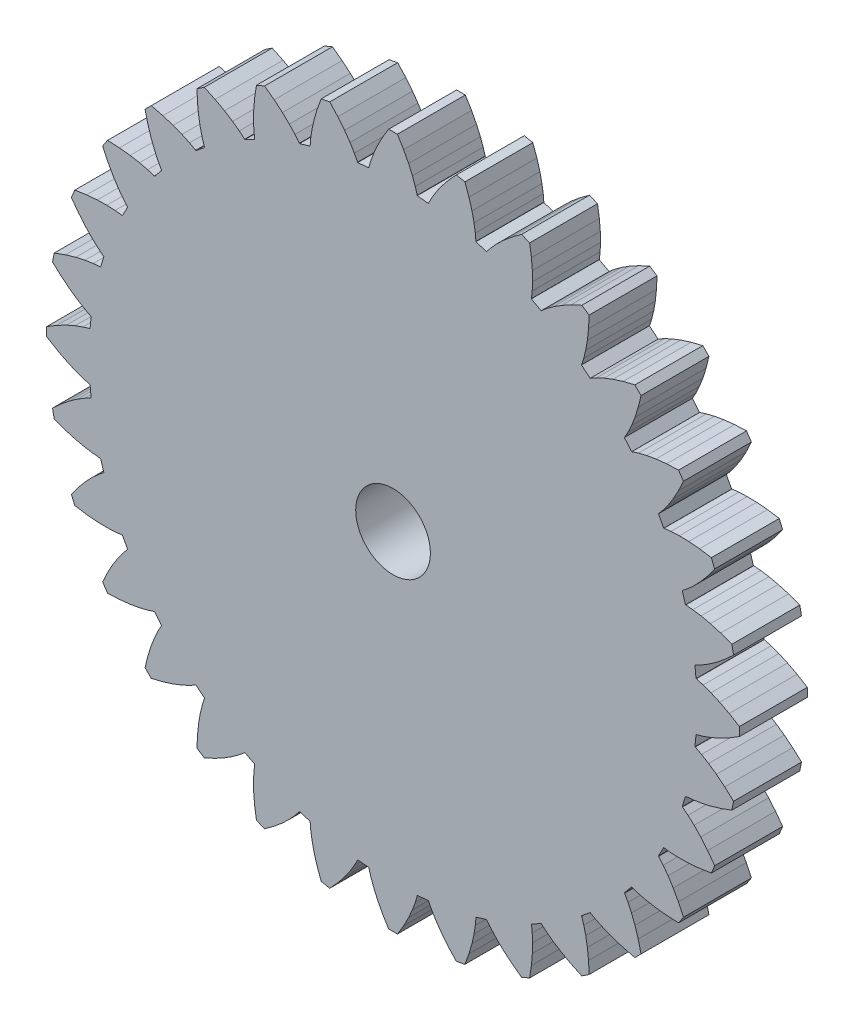
SolidWorks part; units mm, degrees
ref_plane "Front Plane" through (0, 0, 0) normal (0, 0, 1) x (1, 0, 0)
ref_plane "Top Plane" through (0, 0, 0) normal (0, 1, 0) x (1, 0, 0)
ref_plane "Right Plane" through (0, 0, 0) normal (1, 0, 0) x (0, 0, -1)
ref_plane "Plane1" through (0, 0, 5) normal (0, 0, 1) x (1, 0, 0)
sketch "Sketch1" plane through (0, 0, 5) normal (0, 0, 1) x (1, 0, 0)
  line L0 (1.7786, 22.3061) -> (1.7805, 22.3291)
  line L1 (1.7805, 22.3291) -> (1.6348, 22.8279)
  line L2 (1.6348, 22.8279) -> (1.426, 23.4012)
  line L3 (1.426, 23.4012) -> (1.1438, 24.0424)
  line L4 (1.1438, 24.0424) -> (0.7785, 24.7442)
  line L5 (0.7785, 24.7442) -> (0, 26.028)
  line L6 (0, 26.028) -> (-0.7785, 24.7442)
  line L7 (-0.7785, 24.7442) -> (-1.1437, 24.0424)
  line L8 (-1.1437, 24.0424) -> (-1.426, 23.4012)
  line L9 (-1.426, 23.4012) -> (-1.6348, 22.8279)
  line L10 (-1.6348, 22.8279) -> (-1.7805, 22.3291)
  line L11 (-1.7805, 22.3291) -> (-1.7786, 22.3061)
  line L12 (-1.7786, 22.3061) -> (-2.6072, 22.2245)
  line L13 (-2.6072, 22.2245) -> (-2.6099, 22.2474)
  line L14 (-2.6099, 22.2474) -> (-2.8501, 22.7082)
  line L15 (-2.8501, 22.7082) -> (-3.1668, 23.2297)
  line L16 (-3.1668, 23.2297) -> (-3.5687, 23.8036)
  line L17 (-3.5687, 23.8036) -> (-4.0638, 24.4206)
  line L18 (-4.0638, 24.4206) -> (-5.0778, 25.5278)
  line L19 (-5.0778, 25.5278) -> (-5.5909, 24.1168)
  line L20 (-5.5909, 24.1168) -> (-5.8122, 23.3573)
  line L21 (-5.8122, 23.3573) -> (-5.9639, 22.6733)
  line L22 (-5.9639, 22.6733) -> (-6.0569, 22.0703)
  line L23 (-6.0569, 22.0703) -> (-6.1025, 21.5527)
  line L24 (-6.1025, 21.5527) -> (-6.0962, 21.5305)
  line L25 (-6.0962, 21.5305) -> (-6.8929, 21.2888)
  line L26 (-6.8929, 21.2888) -> (-6.9, 21.3108)
  line L27 (-6.9, 21.3108) -> (-7.2255, 21.7159)
  line L28 (-7.2255, 21.7159) -> (-7.6378, 22.1656)
  line L29 (-7.6378, 22.1656) -> (-8.1439, 22.65)
  line L30 (-8.1439, 22.65) -> (-8.7499, 23.1586)
  line L31 (-8.7499, 23.1586) -> (-9.9605, 24.0466)
  line L32 (-9.9605, 24.0466) -> (-10.1884, 22.5627)
  line L33 (-10.1884, 22.5627) -> (-10.2573, 21.7746)
  line L34 (-10.2573, 21.7746) -> (-10.2727, 21.0742)
  line L35 (-10.2727, 21.0742) -> (-10.2462, 20.4646)
  line L36 (-10.2462, 20.4646) -> (-10.1899, 19.948)
  line L37 (-10.1899, 19.948) -> (-10.1794, 19.9275)
  line L38 (-10.1794, 19.9275) -> (-10.9137, 19.535)
  line L39 (-10.9137, 19.535) -> (-10.925, 19.5551)
  line L40 (-10.925, 19.5551) -> (-11.3232, 19.889)
  line L41 (-11.3232, 19.889) -> (-11.8153, 20.2496)
  line L42 (-11.8153, 20.2496) -> (-12.4062, 20.626)
  line L43 (-12.4062, 20.626) -> (-13.0998, 21.0065)
  line L44 (-13.0998, 21.0065) -> (-14.4603, 21.6414)
  line L45 (-14.4603, 21.6414) -> (-14.3944, 20.1415)
  line L46 (-14.3944, 20.1415) -> (-14.3082, 19.3551)
  line L47 (-14.3082, 19.3551) -> (-14.1866, 18.6651)
  line L48 (-14.1866, 18.6651) -> (-14.0418, 18.0724)
  line L49 (-14.0418, 18.0724) -> (-13.8858, 17.5768)
  line L50 (-13.8858, 17.5768) -> (-13.8715, 17.5587)
  line L51 (-13.8715, 17.5587) -> (-14.5151, 17.0305)
  line L52 (-14.5151, 17.0305) -> (-14.5301, 17.048)
  line L53 (-14.5301, 17.048) -> (-14.9858, 17.2977)
  line L54 (-14.9858, 17.2977) -> (-15.5388, 17.5555)
  line L55 (-15.5388, 17.5555) -> (-16.1918, 17.8093)
  line L56 (-16.1918, 17.8093) -> (-16.9463, 18.0473)
  line L57 (-16.9463, 18.0473) -> (-18.4044, 18.4044)
  line L58 (-18.4044, 18.4044) -> (-18.0473, 16.9463)
  line L59 (-18.0473, 16.9463) -> (-17.8093, 16.1918)
  line L60 (-17.8093, 16.1918) -> (-17.5555, 15.5388)
  line L61 (-17.5555, 15.5388) -> (-17.2977, 14.9858)
  line L62 (-17.2977, 14.9858) -> (-17.048, 14.5301)
  line L63 (-17.048, 14.5301) -> (-17.0305, 14.5151)
  line L64 (-17.0305, 14.5151) -> (-17.5587, 13.8715)
  line L65 (-17.5587, 13.8715) -> (-17.5768, 13.8858)
  line L66 (-17.5768, 13.8858) -> (-18.0724, 14.0418)
  line L67 (-18.0724, 14.0418) -> (-18.6651, 14.1866)
  line L68 (-18.6651, 14.1866) -> (-19.3551, 14.3082)
  line L69 (-19.3551, 14.3082) -> (-20.1415, 14.3944)
  line L70 (-20.1415, 14.3944) -> (-21.6414, 14.4603)
  line L71 (-21.6414, 14.4603) -> (-21.0065, 13.0998)
  line L72 (-21.0065, 13.0998) -> (-20.626, 12.4062)
  line L73 (-20.626, 12.4062) -> (-20.2496, 11.8153)
  line L74 (-20.2496, 11.8153) -> (-19.889, 11.3232)
  line L75 (-19.889, 11.3232) -> (-19.5551, 10.925)
  line L76 (-19.5551, 10.925) -> (-19.535, 10.9137)
  line L77 (-19.535, 10.9137) -> (-19.9275, 10.1794)
  line L78 (-19.9275, 10.1794) -> (-19.948, 10.1899)
  line L79 (-19.948, 10.1899) -> (-20.4646, 10.2462)
  line L80 (-20.4646, 10.2462) -> (-21.0742, 10.2727)
  line L81 (-21.0742, 10.2727) -> (-21.7746, 10.2573)
  line L82 (-21.7746, 10.2573) -> (-22.5627, 10.1884)
  line L83 (-22.5627, 10.1884) -> (-24.0466, 9.9605)
  line L84 (-24.0466, 9.9605) -> (-23.1586, 8.7499)
  line L85 (-23.1586, 8.7499) -> (-22.65, 8.1439)
  line L86 (-22.65, 8.1439) -> (-22.1656, 7.6378)
  line L87 (-22.1656, 7.6378) -> (-21.7159, 7.2255)
  line L88 (-21.7159, 7.2255) -> (-21.3108, 6.9)
  line L89 (-21.3108, 6.9) -> (-21.2888, 6.8929)
  line L90 (-21.2888, 6.8929) -> (-21.5305, 6.0962)
  line L91 (-21.5305, 6.0962) -> (-21.5527, 6.1025)
  line L92 (-21.5527, 6.1025) -> (-22.0703, 6.0569)
  line L93 (-22.0703, 6.0569) -> (-22.6733, 5.9639)
  line L94 (-22.6733, 5.9639) -> (-23.3573, 5.8122)
  line L95 (-23.3573, 5.8122) -> (-24.1168, 5.5909)
  line L96 (-24.1168, 5.5909) -> (-25.5278, 5.0778)
  line L97 (-25.5278, 5.0778) -> (-24.4206, 4.0638)
  line L98 (-24.4206, 4.0638) -> (-23.8036, 3.5687)
  line L99 (-23.8036, 3.5687) -> (-23.2297, 3.1668)
  line L100 (-23.2297, 3.1668) -> (-22.7082, 2.8501)
  line L101 (-22.7082, 2.8501) -> (-22.2474, 2.6099)
  line L102 (-22.2474, 2.6099) -> (-22.2245, 2.6072)
  line L103 (-22.2245, 2.6072) -> (-22.3061, 1.7786)
  line L104 (-22.3061, 1.7786) -> (-22.3291, 1.7805)
  line L105 (-22.3291, 1.7805) -> (-22.8279, 1.6348)
  line L106 (-22.8279, 1.6348) -> (-23.4012, 1.426)
  line L107 (-23.4012, 1.426) -> (-24.0424, 1.1438)
  line L108 (-24.0424, 1.1438) -> (-24.7442, 0.7785)
  line L109 (-24.7442, 0.7785) -> (-26.028, 0)
  line L110 (-26.028, 0) -> (-24.7442, -0.7785)
  line L111 (-24.7442, -0.7785) -> (-24.0424, -1.1437)
  line L112 (-24.0424, -1.1437) -> (-23.4012, -1.426)
  line L113 (-23.4012, -1.426) -> (-22.8279, -1.6348)
  line L114 (-22.8279, -1.6348) -> (-22.3291, -1.7805)
  line L115 (-22.3291, -1.7805) -> (-22.3061, -1.7786)
  line L116 (-22.3061, -1.7786) -> (-22.2245, -2.6072)
  line L117 (-22.2245, -2.6072) -> (-22.2474, -2.6099)
  line L118 (-22.2474, -2.6099) -> (-22.7082, -2.8501)
  line L119 (-22.7082, -2.8501) -> (-23.2297, -3.1668)
  line L120 (-23.2297, -3.1668) -> (-23.8036, -3.5687)
  line L121 (-23.8036, -3.5687) -> (-24.4206, -4.0638)
  line L122 (-24.4206, -4.0638) -> (-25.5278, -5.0778)
  line L123 (-25.5278, -5.0778) -> (-24.1168, -5.5909)
  line L124 (-24.1168, -5.5909) -> (-23.3573, -5.8122)
  line L125 (-23.3573, -5.8122) -> (-22.6733, -5.9639)
  line L126 (-22.6733, -5.9639) -> (-22.0703, -6.0569)
  line L127 (-22.0703, -6.0569) -> (-21.5527, -6.1025)
  line L128 (-21.5527, -6.1025) -> (-21.5305, -6.0962)
  line L129 (-21.5305, -6.0962) -> (-21.2888, -6.8929)
  line L130 (-21.2888, -6.8929) -> (-21.3108, -6.9)
  line L131 (-21.3108, -6.9) -> (-21.7159, -7.2255)
  line L132 (-21.7159, -7.2255) -> (-22.1656, -7.6378)
  line L133 (-22.1656, -7.6378) -> (-22.65, -8.1439)
  line L134 (-22.65, -8.1439) -> (-23.1586, -8.7499)
  line L135 (-23.1586, -8.7499) -> (-24.0466, -9.9605)
  line L136 (-24.0466, -9.9605) -> (-22.5627, -10.1884)
  line L137 (-22.5627, -10.1884) -> (-21.7746, -10.2573)
  line L138 (-21.7746, -10.2573) -> (-21.0742, -10.2727)
  line L139 (-21.0742, -10.2727) -> (-20.4646, -10.2462)
  line L140 (-20.4646, -10.2462) -> (-19.948, -10.1899)
  line L141 (-19.948, -10.1899) -> (-19.9275, -10.1794)
  line L142 (-19.9275, -10.1794) -> (-19.535, -10.9137)
  line L143 (-19.535, -10.9137) -> (-19.5551, -10.925)
  line L144 (-19.5551, -10.925) -> (-19.889, -11.3232)
  line L145 (-19.889, -11.3232) -> (-20.2496, -11.8153)
  line L146 (-20.2496, -11.8153) -> (-20.626, -12.4062)
  line L147 (-20.626, -12.4062) -> (-21.0065, -13.0998)
  line L148 (-21.0065, -13.0998) -> (-21.6414, -14.4603)
  line L149 (-21.6414, -14.4603) -> (-20.1415, -14.3944)
  line L150 (-20.1415, -14.3944) -> (-19.3551, -14.3082)
  line L151 (-19.3551, -14.3082) -> (-18.6651, -14.1866)
  line L152 (-18.6651, -14.1866) -> (-18.0724, -14.0418)
  line L153 (-18.0724, -14.0418) -> (-17.5768, -13.8858)
  line L154 (-17.5768, -13.8858) -> (-17.5587, -13.8715)
  line L155 (-17.5587, -13.8715) -> (-17.0305, -14.5151)
  line L156 (-17.0305, -14.5151) -> (-17.048, -14.5301)
  line L157 (-17.048, -14.5301) -> (-17.2977, -14.9858)
  line L158 (-17.2977, -14.9858) -> (-17.5555, -15.5388)
  line L159 (-17.5555, -15.5388) -> (-17.8093, -16.1918)
  line L160 (-17.8093, -16.1918) -> (-18.0473, -16.9463)
  line L161 (-18.0473, -16.9463) -> (-18.4044, -18.4044)
  line L162 (-18.4044, -18.4044) -> (-16.9463, -18.0473)
  line L163 (-16.9463, -18.0473) -> (-16.1918, -17.8093)
  line L164 (-16.1918, -17.8093) -> (-15.5388, -17.5555)
  line L165 (-15.5388, -17.5555) -> (-14.9858, -17.2977)
  line L166 (-14.9858, -17.2977) -> (-14.5301, -17.048)
  line L167 (-14.5301, -17.048) -> (-14.5151, -17.0305)
  line L168 (-14.5151, -17.0305) -> (-13.8715, -17.5587)
  line L169 (-13.8715, -17.5587) -> (-13.8858, -17.5768)
  line L170 (-13.8858, -17.5768) -> (-14.0418, -18.0724)
  line L171 (-14.0418, -18.0724) -> (-14.1866, -18.6651)
  line L172 (-14.1866, -18.6651) -> (-14.3082, -19.3551)
  line L173 (-14.3082, -19.3551) -> (-14.3944, -20.1415)
  line L174 (-14.3944, -20.1415) -> (-14.4603, -21.6414)
  line L175 (-14.4603, -21.6414) -> (-13.0998, -21.0065)
  line L176 (-13.0998, -21.0065) -> (-12.4062, -20.626)
  line L177 (-12.4062, -20.626) -> (-11.8153, -20.2496)
  line L178 (-11.8153, -20.2496) -> (-11.3232, -19.889)
  line L179 (-11.3232, -19.889) -> (-10.925, -19.5551)
  line L180 (-10.925, -19.5551) -> (-10.9137, -19.535)
  line L181 (-10.9137, -19.535) -> (-10.1794, -19.9275)
  line L182 (-10.1794, -19.9275) -> (-10.1899, -19.948)
  line L183 (-10.1899, -19.948) -> (-10.2462, -20.4646)
  line L184 (-10.2462, -20.4646) -> (-10.2727, -21.0742)
  line L185 (-10.2727, -21.0742) -> (-10.2573, -21.7746)
  line L186 (-10.2573, -21.7746) -> (-10.1884, -22.5627)
  line L187 (-10.1884, -22.5627) -> (-9.9605, -24.0466)
  line L188 (-9.9605, -24.0466) -> (-8.7499, -23.1586)
  line L189 (-8.7499, -23.1586) -> (-8.1439, -22.65)
  line L190 (-8.1439, -22.65) -> (-7.6378, -22.1656)
  line L191 (-7.6378, -22.1656) -> (-7.2255, -21.7159)
  line L192 (-7.2255, -21.7159) -> (-6.9, -21.3108)
  line L193 (-6.9, -21.3108) -> (-6.8929, -21.2888)
  line L194 (-6.8929, -21.2888) -> (-6.0962, -21.5305)
  line L195 (-6.0962, -21.5305) -> (-6.1025, -21.5527)
  line L196 (-6.1025, -21.5527) -> (-6.0569, -22.0703)
  line L197 (-6.0569, -22.0703) -> (-5.9639, -22.6733)
  line L198 (-5.9639, -22.6733) -> (-5.8122, -23.3573)
  line L199 (-5.8122, -23.3573) -> (-5.5909, -24.1168)
  line L200 (-5.5909, -24.1168) -> (-5.0778, -25.5278)
  line L201 (-5.0778, -25.5278) -> (-4.0638, -24.4206)
  line L202 (-4.0638, -24.4206) -> (-3.5687, -23.8036)
  line L203 (-3.5687, -23.8036) -> (-3.1668, -23.2297)
  line L204 (-3.1668, -23.2297) -> (-2.8501, -22.7082)
  line L205 (-2.8501, -22.7082) -> (-2.6099, -22.2474)
  line L206 (-2.6099, -22.2474) -> (-2.6072, -22.2245)
  line L207 (-2.6072, -22.2245) -> (-1.7786, -22.3061)
  line L208 (-1.7786, -22.3061) -> (-1.7805, -22.3291)
  line L209 (-1.7805, -22.3291) -> (-1.6348, -22.8279)
  line L210 (-1.6348, -22.8279) -> (-1.426, -23.4012)
  line L211 (-1.426, -23.4012) -> (-1.1438, -24.0424)
  line L212 (-1.1438, -24.0424) -> (-0.7785, -24.7442)
  line L213 (-0.7785, -24.7442) -> (0, -26.028)
  line L214 (0, -26.028) -> (0.7785, -24.7442)
  line L215 (0.7785, -24.7442) -> (1.1437, -24.0424)
  line L216 (1.1437, -24.0424) -> (1.426, -23.4012)
  line L217 (1.426, -23.4012) -> (1.6348, -22.8279)
  line L218 (1.6348, -22.8279) -> (1.7805, -22.3291)
  line L219 (1.7805, -22.3291) -> (1.7786, -22.3061)
  line L220 (1.7786, -22.3061) -> (2.6072, -22.2245)
  line L221 (2.6072, -22.2245) -> (2.6099, -22.2474)
  line L222 (2.6099, -22.2474) -> (2.8501, -22.7082)
  line L223 (2.8501, -22.7082) -> (3.1668, -23.2297)
  line L224 (3.1668, -23.2297) -> (3.5687, -23.8036)
  line L225 (3.5687, -23.8036) -> (4.0638, -24.4206)
  line L226 (4.0638, -24.4206) -> (5.0778, -25.5278)
  line L227 (5.0778, -25.5278) -> (5.5909, -24.1168)
  line L228 (5.5909, -24.1168) -> (5.8122, -23.3573)
  line L229 (5.8122, -23.3573) -> (5.9639, -22.6733)
  line L230 (5.9639, -22.6733) -> (6.0569, -22.0703)
  line L231 (6.0569, -22.0703) -> (6.1025, -21.5527)
  line L232 (6.1025, -21.5527) -> (6.0962, -21.5305)
  line L233 (6.0962, -21.5305) -> (6.8929, -21.2888)
  line L234 (6.8929, -21.2888) -> (6.9, -21.3108)
  line L235 (6.9, -21.3108) -> (7.2255, -21.7159)
  line L236 (7.2255, -21.7159) -> (7.6378, -22.1656)
  line L237 (7.6378, -22.1656) -> (8.1439, -22.65)
  line L238 (8.1439, -22.65) -> (8.7499, -23.1586)
  line L239 (8.7499, -23.1586) -> (9.9605, -24.0466)
  line L240 (9.9605, -24.0466) -> (10.1884, -22.5627)
  line L241 (10.1884, -22.5627) -> (10.2573, -21.7746)
  line L242 (10.2573, -21.7746) -> (10.2727, -21.0742)
  line L243 (10.2727, -21.0742) -> (10.2462, -20.4646)
  line L244 (10.2462, -20.4646) -> (10.1899, -19.948)
  line L245 (10.1899, -19.948) -> (10.1794, -19.9275)
  line L246 (10.1794, -19.9275) -> (10.9137, -19.535)
  line L247 (10.9137, -19.535) -> (10.925, -19.5551)
  line L248 (10.925, -19.5551) -> (11.3232, -19.889)
  line L249 (11.3232, -19.889) -> (11.8153, -20.2496)
  line L250 (11.8153, -20.2496) -> (12.4062, -20.626)
  line L251 (12.4062, -20.626) -> (13.0998, -21.0065)
  line L252 (13.0998, -21.0065) -> (14.4603, -21.6414)
  line L253 (14.4603, -21.6414) -> (14.3944, -20.1415)
  line L254 (14.3944, -20.1415) -> (14.3082, -19.3551)
  line L255 (14.3082, -19.3551) -> (14.1866, -18.6651)
  line L256 (14.1866, -18.6651) -> (14.0418, -18.0724)
  line L257 (14.0418, -18.0724) -> (13.8858, -17.5768)
  line L258 (13.8858, -17.5768) -> (13.8715, -17.5587)
  line L259 (13.8715, -17.5587) -> (14.5151, -17.0305)
  line L260 (14.5151, -17.0305) -> (14.5301, -17.048)
  line L261 (14.5301, -17.048) -> (14.9858, -17.2977)
  line L262 (14.9858, -17.2977) -> (15.5388, -17.5555)
  line L263 (15.5388, -17.5555) -> (16.1918, -17.8093)
  line L264 (16.1918, -17.8093) -> (16.9463, -18.0473)
  line L265 (16.9463, -18.0473) -> (18.4044, -18.4044)
  line L266 (18.4044, -18.4044) -> (18.0473, -16.9463)
  line L267 (18.0473, -16.9463) -> (17.8093, -16.1918)
  line L268 (17.8093, -16.1918) -> (17.5555, -15.5388)
  line L269 (17.5555, -15.5388) -> (17.2977, -14.9858)
  line L270 (17.2977, -14.9858) -> (17.048, -14.5301)
  line L271 (17.048, -14.5301) -> (17.0305, -14.5151)
  line L272 (17.0305, -14.5151) -> (17.5587, -13.8715)
  line L273 (17.5587, -13.8715) -> (17.5768, -13.8858)
  line L274 (17.5768, -13.8858) -> (18.0724, -14.0418)
  line L275 (18.0724, -14.0418) -> (18.6651, -14.1866)
  line L276 (18.6651, -14.1866) -> (19.3551, -14.3082)
  line L277 (19.3551, -14.3082) -> (20.1415, -14.3944)
  line L278 (20.1415, -14.3944) -> (21.6414, -14.4603)
  line L279 (21.6414, -14.4603) -> (21.0065, -13.0998)
  line L280 (21.0065, -13.0998) -> (20.626, -12.4062)
  line L281 (20.626, -12.4062) -> (20.2496, -11.8153)
  line L282 (20.2496, -11.8153) -> (19.889, -11.3232)
  line L283 (19.889, -11.3232) -> (19.5551, -10.925)
  line L284 (19.5551, -10.925) -> (19.535, -10.9137)
  line L285 (19.535, -10.9137) -> (19.9275, -10.1794)
  line L286 (19.9275, -10.1794) -> (19.948, -10.1899)
  line L287 (19.948, -10.1899) -> (20.4646, -10.2462)
  line L288 (20.4646, -10.2462) -> (21.0742, -10.2727)
  line L289 (21.0742, -10.2727) -> (21.7746, -10.2573)
  line L290 (21.7746, -10.2573) -> (22.5627, -10.1884)
  line L291 (22.5627, -10.1884) -> (24.0466, -9.9605)
  line L292 (24.0466, -9.9605) -> (23.1586, -8.7499)
  line L293 (23.1586, -8.7499) -> (22.65, -8.1439)
  line L294 (22.65, -8.1439) -> (22.1656, -7.6378)
  line L295 (22.1656, -7.6378) -> (21.7159, -7.2255)
  line L296 (21.7159, -7.2255) -> (21.3108, -6.9)
  line L297 (21.3108, -6.9) -> (21.2888, -6.8929)
  line L298 (21.2888, -6.8929) -> (21.5305, -6.0962)
  line L299 (21.5305, -6.0962) -> (21.5527, -6.1025)
  line L300 (21.5527, -6.1025) -> (22.0703, -6.0569)
  line L301 (22.0703, -6.0569) -> (22.6733, -5.9639)
  line L302 (22.6733, -5.9639) -> (23.3573, -5.8122)
  line L303 (23.3573, -5.8122) -> (24.1168, -5.5909)
  line L304 (24.1168, -5.5909) -> (25.5278, -5.0778)
  line L305 (25.5278, -5.0778) -> (24.4206, -4.0638)
  line L306 (24.4206, -4.0638) -> (23.8036, -3.5687)
  line L307 (23.8036, -3.5687) -> (23.2297, -3.1668)
  line L308 (23.2297, -3.1668) -> (22.7082, -2.8501)
  line L309 (22.7082, -2.8501) -> (22.2474, -2.6099)
  line L310 (22.2474, -2.6099) -> (22.2245, -2.6072)
  line L311 (22.2245, -2.6072) -> (22.3061, -1.7786)
  line L312 (22.3061, -1.7786) -> (22.3291, -1.7805)
  line L313 (22.3291, -1.7805) -> (22.8279, -1.6348)
  line L314 (22.8279, -1.6348) -> (23.4012, -1.426)
  line L315 (23.4012, -1.426) -> (24.0424, -1.1438)
  line L316 (24.0424, -1.1438) -> (24.7442, -0.7785)
  line L317 (24.7442, -0.7785) -> (26.028, 0)
  line L318 (26.028, 0) -> (24.7442, 0.7785)
  line L319 (24.7442, 0.7785) -> (24.0424, 1.1437)
  line L320 (24.0424, 1.1437) -> (23.4012, 1.426)
  line L321 (23.4012, 1.426) -> (22.8279, 1.6348)
  line L322 (22.8279, 1.6348) -> (22.3291, 1.7805)
  line L323 (22.3291, 1.7805) -> (22.3061, 1.7786)
  line L324 (22.3061, 1.7786) -> (22.2245, 2.6072)
  line L325 (22.2245, 2.6072) -> (22.2474, 2.6099)
  line L326 (22.2474, 2.6099) -> (22.7082, 2.8501)
  line L327 (22.7082, 2.8501) -> (23.2297, 3.1668)
  line L328 (23.2297, 3.1668) -> (23.8036, 3.5687)
  line L329 (23.8036, 3.5687) -> (24.4206, 4.0638)
  line L330 (24.4206, 4.0638) -> (25.5278, 5.0778)
  line L331 (25.5278, 5.0778) -> (24.1168, 5.5909)
  line L332 (24.1168, 5.5909) -> (23.3573, 5.8122)
  line L333 (23.3573, 5.8122) -> (22.6733, 5.9639)
  line L334 (22.6733, 5.9639) -> (22.0703, 6.0569)
  line L335 (22.0703, 6.0569) -> (21.5527, 6.1025)
  line L336 (21.5527, 6.1025) -> (21.5305, 6.0962)
  line L337 (21.5305, 6.0962) -> (21.2888, 6.8929)
  line L338 (21.2888, 6.8929) -> (21.3108, 6.9)
  line L339 (21.3108, 6.9) -> (21.7159, 7.2255)
  line L340 (21.7159, 7.2255) -> (22.1656, 7.6378)
  line L341 (22.1656, 7.6378) -> (22.65, 8.1439)
  line L342 (22.65, 8.1439) -> (23.1586, 8.7499)
  line L343 (23.1586, 8.7499) -> (24.0466, 9.9605)
  line L344 (24.0466, 9.9605) -> (22.5627, 10.1884)
  line L345 (22.5627, 10.1884) -> (21.7746, 10.2573)
  line L346 (21.7746, 10.2573) -> (21.0742, 10.2727)
  line L347 (21.0742, 10.2727) -> (20.4646, 10.2462)
  line L348 (20.4646, 10.2462) -> (19.948, 10.1899)
  line L349 (19.948, 10.1899) -> (19.9275, 10.1794)
  line L350 (19.9275, 10.1794) -> (19.535, 10.9137)
  line L351 (19.535, 10.9137) -> (19.5551, 10.925)
  line L352 (19.5551, 10.925) -> (19.889, 11.3232)
  line L353 (19.889, 11.3232) -> (20.2496, 11.8153)
  line L354 (20.2496, 11.8153) -> (20.626, 12.4062)
  line L355 (20.626, 12.4062) -> (21.0065, 13.0998)
  line L356 (21.0065, 13.0998) -> (21.6414, 14.4603)
  line L357 (21.6414, 14.4603) -> (20.1415, 14.3944)
  line L358 (20.1415, 14.3944) -> (19.3551, 14.3082)
  line L359 (19.3551, 14.3082) -> (18.6651, 14.1866)
  line L360 (18.6651, 14.1866) -> (18.0724, 14.0418)
  line L361 (18.0724, 14.0418) -> (17.5768, 13.8858)
  line L362 (17.5768, 13.8858) -> (17.5587, 13.8715)
  line L363 (17.5587, 13.8715) -> (17.0305, 14.5151)
  line L364 (17.0305, 14.5151) -> (17.048, 14.5301)
  line L365 (17.048, 14.5301) -> (17.2977, 14.9858)
  line L366 (17.2977, 14.9858) -> (17.5555, 15.5388)
  line L367 (17.5555, 15.5388) -> (17.8093, 16.1918)
  line L368 (17.8093, 16.1918) -> (18.0473, 16.9463)
  line L369 (18.0473, 16.9463) -> (18.4044, 18.4044)
  line L370 (18.4044, 18.4044) -> (16.9463, 18.0473)
  line L371 (16.9463, 18.0473) -> (16.1918, 17.8093)
  line L372 (16.1918, 17.8093) -> (15.5388, 17.5555)
  line L373 (15.5388, 17.5555) -> (14.9858, 17.2977)
  line L374 (14.9858, 17.2977) -> (14.5301, 17.048)
  line L375 (14.5301, 17.048) -> (14.5151, 17.0305)
  line L376 (14.5151, 17.0305) -> (13.8715, 17.5587)
  line L377 (13.8715, 17.5587) -> (13.8858, 17.5768)
  line L378 (13.8858, 17.5768) -> (14.0418, 18.0724)
  line L379 (14.0418, 18.0724) -> (14.1866, 18.6651)
  line L380 (14.1866, 18.6651) -> (14.3082, 19.3551)
  line L381 (14.3082, 19.3551) -> (14.3944, 20.1415)
  line L382 (14.3944, 20.1415) -> (14.4603, 21.6414)
  line L383 (14.4603, 21.6414) -> (13.0998, 21.0065)
  line L384 (13.0998, 21.0065) -> (12.4062, 20.626)
  line L385 (12.4062, 20.626) -> (11.8153, 20.2496)
  line L386 (11.8153, 20.2496) -> (11.3232, 19.889)
  line L387 (11.3232, 19.889) -> (10.925, 19.5551)
  line L388 (10.925, 19.5551) -> (10.9137, 19.535)
  line L389 (10.9137, 19.535) -> (10.1794, 19.9275)
  line L390 (10.1794, 19.9275) -> (10.1899, 19.948)
  line L391 (10.1899, 19.948) -> (10.2462, 20.4646)
  line L392 (10.2462, 20.4646) -> (10.2727, 21.0742)
  line L393 (10.2727, 21.0742) -> (10.2573, 21.7746)
  line L394 (10.2573, 21.7746) -> (10.1884, 22.5627)
  line L395 (10.1884, 22.5627) -> (9.9605, 24.0466)
  line L396 (9.9605, 24.0466) -> (8.7499, 23.1586)
  line L397 (8.7499, 23.1586) -> (8.1439, 22.65)
  line L398 (8.1439, 22.65) -> (7.6378, 22.1656)
  line L399 (7.6378, 22.1656) -> (7.2255, 21.7159)
  line L400 (7.2255, 21.7159) -> (6.9, 21.3108)
  line L401 (6.9, 21.3108) -> (6.8929, 21.2888)
  line L402 (6.8929, 21.2888) -> (6.0962, 21.5305)
  line L403 (6.0962, 21.5305) -> (6.1025, 21.5527)
  line L404 (6.1025, 21.5527) -> (6.0569, 22.0703)
  line L405 (6.0569, 22.0703) -> (5.9639, 22.6733)
  line L406 (5.9639, 22.6733) -> (5.8122, 23.3573)
  line L407 (5.8122, 23.3573) -> (5.5909, 24.1168)
  line L408 (5.5909, 24.1168) -> (5.0778, 25.5278)
  line L409 (5.0778, 25.5278) -> (4.0638, 24.4206)
  line L410 (4.0638, 24.4206) -> (3.5687, 23.8036)
  line L411 (3.5687, 23.8036) -> (3.1668, 23.2297)
  line L412 (3.1668, 23.2297) -> (2.8501, 22.7082)
  line L413 (2.8501, 22.7082) -> (2.6099, 22.2474)
  line L414 (2.6099, 22.2474) -> (2.6072, 22.2245)
  line L415 (2.6072, 22.2245) -> (1.7786, 22.3061)
extrude "Boss-Extrude1" add sketch "Sketch1" against normal blind 5
sketch "Sketch2" plane through (0, 0, 5) normal (0, 0, 1) x (1, 0, 0)
  line L0 (-7.5, 0) -> (-7.2444, 1.9411)
  line L1 (-7.2444, 1.9411) -> (-6.4952, 3.75)
  line L2 (-6.4952, 3.75) -> (-5.3033, 5.3033)
  line L3 (-5.3033, 5.3033) -> (-3.75, 6.4952)
  line L4 (-3.75, 6.4952) -> (-1.9411, 7.2444)
  line L5 (-1.9411, 7.2444) -> (0, 7.5)
  line L6 (0, 7.5) -> (1.9411, 7.2444)
  line L7 (1.9411, 7.2444) -> (3.75, 6.4952)
  line L8 (3.75, 6.4952) -> (5.3033, 5.3033)
  line L9 (5.3033, 5.3033) -> (6.4952, 3.75)
  line L10 (6.4952, 3.75) -> (7.2444, 1.9411)
  line L11 (7.2444, 1.9411) -> (7.5, 0)
  line L12 (7.5, 0) -> (7.2444, -1.9411)
  line L13 (7.2444, -1.9411) -> (6.4952, -3.75)
  line L14 (6.4952, -3.75) -> (5.3033, -5.3033)
  line L15 (5.3033, -5.3033) -> (3.75, -6.4952)
  line L16 (3.75, -6.4952) -> (1.9411, -7.2444)
  line L17 (1.9411, -7.2444) -> (0, -7.5)
  line L18 (0, -7.5) -> (-1.9411, -7.2444)
  line L19 (-1.9411, -7.2444) -> (-3.75, -6.4952)
  line L20 (-3.75, -6.4952) -> (-5.3033, -5.3033)
  line L21 (-5.3033, -5.3033) -> (-6.4952, -3.75)
  line L22 (-6.4952, -3.75) -> (-7.2444, -1.9411)
  line L23 (-7.2444, -1.9411) -> (-7.5, 0)
extrude "Boss-Extrude2" add sketch "Sketch2" along normal blind 10
sketch "Sketch3" plane through (0, 0, 0) normal (0, 0, -1) x (-1, 0, 0)
  line L0 (1.7678, 1.7678) -> (0, 2.5)
  line L1 (0, 2.5) -> (-1.7678, 1.7678)
  line L2 (-1.7678, 1.7678) -> (-2.5, 0)
  line L3 (-2.5, 0) -> (-1.7678, -1.7678)
  line L4 (-1.7678, -1.7678) -> (0, -2.5)
  line L5 (0, -2.5) -> (1.7678, -1.7678)
  line L6 (1.7678, -1.7678) -> (2.5, 0)
  line L7 (2.5, 0) -> (1.7678, 1.7678)
extrude "Cut-Extrude1" cut sketch "Sketch3" against normal through all
chamfer "Chamfer1" distance 0.6198 angle 58.767 4 edges at (25.5278, -5.0778, 2.5) (-25.5278, 5.0778, 2.5) (-5.0778, 25.5278, 2.5) (-5.0778, -25.5278, 2.5) first distance on face at (24.8223, -5.3344, 2.5) first distance on face at (-24.8223, 5.3344, 2.5) first distance on face at (-4.5708, 24.9742, 2.5) first distance on face at (-5.3344, -24.8223, 2.5)
chamfer "Chamfer2" distance 0.6197 angle 58.779 3 edges at (24.0466, -9.9605, 2.5) (-24.0466, 9.9605, 2.5) (-24.0466, -9.9605, 2.5) first distance on face at (23.6026, -9.3552, 2.5) first distance on face at (-23.6026, 9.3552, 2.5) first distance on face at (-23.3047, -10.0745, 2.5)
chamfer "Chamfer3" distance 0.6198 angle 58.766 2 edges at (26.028, 0, 2.5) (-26.028, 0, 2.5) first distance on face at (25.3861, -0.3893, 2.5) first distance on face at (-25.3861, 0.3893, 2.5)
chamfer "Chamfer4" distance 0.6198 angle 58.764 4 edges at (-25.5278, -5.0778, 2.5) (5.0778, -25.5278, 2.5) (25.5278, 5.0778, 2.5) (5.0778, 25.5278, 2.5) first distance on face at (-24.8223, -5.3344, 2.5) first distance on face at (5.3344, -24.8223, 2.5) first distance on face at (24.8223, 5.3344, 2.5) first distance on face at (4.5708, 24.9742, 2.5)
chamfer "Chamfer5" distance 0.6197 angle 58.779 3 edges at (9.9605, -24.0466, 2.5) (9.9605, 24.0466, 2.5) (-9.9605, 24.0466, 2.5) first distance on face at (10.0745, -23.3047, 2.5) first distance on face at (9.3552, 23.6026, 2.5) first distance on face at (-10.0745, 23.3047, 2.5)
chamfer "Chamfer6" distance 0.6199 angle 58.753 1 edges at (-9.9605, -24.0466, 2.5) first distance on face at (-9.3552, -23.6026, 2.5)
chamfer "Chamfer7" distance 0.6199 angle 58.753 1 edges at (24.0466, 9.9605, 2.5) first distance on face at (23.6026, 9.3552, 2.5)
chamfer "Chamfer8" distance 0.6197 angle 58.767 4 edges at (14.4603, -21.6414, 2.5) (21.6414, 14.4603, 2.5) (-14.4603, 21.6414, 2.5) (-14.4603, -21.6414, 2.5) first distance on face at (14.4274, -20.8914, 2.5) first distance on face at (20.8914, 14.4274, 2.5) first distance on face at (-14.4274, 20.8914, 2.5) first distance on face at (-13.7801, -21.3239, 2.5)
chamfer "Chamfer9" distance 0.6197 angle 58.762 4 edges at (-18.4044, -18.4044, 2.5) (18.4044, -18.4044, 2.5) (18.4044, 18.4044, 2.5) (-18.4044, 18.4044, 2.5) first distance on face at (-18.2259, -17.6754, 2.5) first distance on face at (17.6754, -18.2259, 2.5) first distance on face at (18.2259, 17.6754, 2.5) first distance on face at (-17.6754, 18.2259, 2.5)
chamfer "Chamfer10" distance 0.6198 angle 58.764 4 edges at (-21.6414, -14.4603, 2.5) (21.6414, -14.4603, 2.5) (-21.6414, 14.4603, 2.5) (14.4603, 21.6414, 2.5) first distance on face at (-21.3239, -13.7801, 2.5) first distance on face at (20.8914, -14.4274, 2.5) first distance on face at (-20.8914, 14.4274, 2.5) first distance on face at (14.4274, 20.8914, 2.5)
chamfer "Chamfer11" distance 0.6198 angle 58.766 2 edges at (0, 26.028, 2.5) (0, -26.028, 2.5) first distance on face at (-0.3893, 25.3861, 2.5) first distance on face at (0.3893, -25.3861, 2.5)
ref_plane "Plane2" through (0, 0, 5) normal (0, 0, 1) x (1, 0, 0)
other "SurfaceCut1" flip cut yes
sketch "Sketch4" plane through (0, 0, 0) normal (0, 0, -1) x (-1, 0, 0)
  circle A0 centre (0, 0) radius 2.75
  dimension "D1" = 5.5
extrude "Cut-Extrude2" cut sketch "Sketch4" against normal up to surface (5 mm away) up to face at (0, 0, 5)
